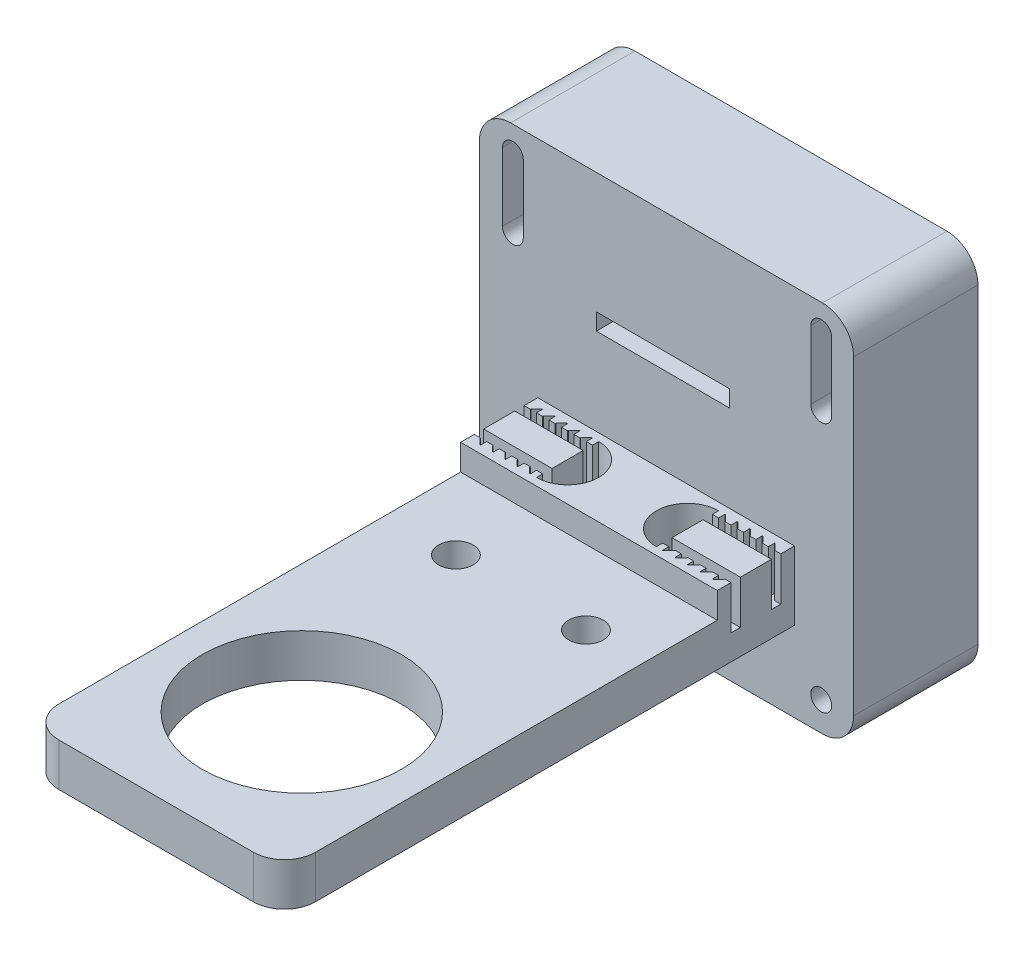
SolidWorks part; units mm, degrees
ref_plane "Alzado" through (0, 0, 0) normal (0, 0, 1) x (1, 0, 0)
ref_plane "Planta" through (0, 0, 0) normal (0, 1, 0) x (1, 0, 0)
ref_plane "Vista lateral" through (0, 0, 0) normal (1, 0, 0) x (0, 0, -1)
sketch "Croquis1" plane through (0, 0, 0) normal (0, 0, 1) x (1, 0, 0)
  line L0 (-21.7038, 24.1707) -> (-21.7038, 13.2033) construction
  line L1 (-27.0724, 28.25) -> (33.0729, 28.25)
  line L2 (-27.0724, 28.25) -> (-27.0724, -31.75)
  line L3 (-27.0724, -31.75) -> (33.0729, -31.75)
  line L4 (33.0729, 28.25) -> (33.0729, -31.75)
  line L5 (-8.2743, 8.8387) -> (13.1009, 8.8387)
  line L6 (-8.2743, 8.8387) -> (-8.2743, 6.1528)
  line L7 (-8.2743, 6.1528) -> (13.1009, 6.1528)
  line L8 (13.1009, 8.8387) -> (13.1009, 6.1528)
  line L9 (-20.0251, 24.1707) -> (-20.0251, 13.2033)
  line L10 (-23.3825, 24.1707) -> (-23.3825, 13.2033)
  line L11 (27.8733, 24.1707) -> (27.8733, 13.2033) construction
  line L12 (29.552, 24.1707) -> (29.552, 13.2033)
  line L13 (26.1946, 24.1707) -> (26.1946, 13.2033)
  circle A2 centre (27.8733, -27.0851) radius 1.6787
  circle A3 centre (-21.7038, -27.0851) radius 1.6787
  arc A4 (-20.0251, 24.1707) -> (-23.3825, 24.1707) centre (-21.7038, 24.1707) ccw
  arc A5 (-23.3825, 13.2033) -> (-20.0251, 13.2033) centre (-21.7038, 13.2033) ccw
  arc A6 (29.552, 24.1707) -> (26.1946, 24.1707) centre (27.8733, 24.1707) ccw
  arc A7 (26.1946, 13.2033) -> (29.552, 13.2033) centre (27.8733, 13.2033) ccw
  point P16 (-21.7038, 18.687)
  point P22 (27.8733, 18.687)
  dimension "D1" = 60.1453
  dimension "D2" = 60
extrude "Saliente-Extruir1" add sketch "Croquis1" along normal blind 20
sketch "Croquis2" plane through (0, 0, 20) normal (0, 0, 1) x (1, 0, 0)
  line L1 (-17.6867, -7.8196) -> (23.5792, -7.8196)
  line L2 (-17.6867, -7.8196) -> (-17.6867, -18.8667)
  line L3 (-17.6867, -18.8667) -> (23.5792, -18.8667)
  line L4 (23.5792, -7.8196) -> (23.5792, -18.8667)
extrude "Saliente-Extruir2" add sketch "Croquis2" along normal blind 82
sketch "Croquis3" plane through (23.5792, 0, 0) normal (1, 0, 0) x (0, 0, -1)
  line L1 (-54.9335, -4.4205) -> (-32.4143, -4.4205)
  line L2 (-54.9335, -4.4205) -> (-54.9335, -11.9623)
  line L3 (-54.9335, -11.9623) -> (-32.4143, -11.9623)
  line L4 (-32.4143, -11.9623) -> (-32.4143, -4.4205)
extrude "Cortar-Extruir1" cut sketch "Croquis3" against normal blind 50
sketch "Croquis4" plane through (0, -18.8667, 0) normal (0, -1, 0) x (1, 0, 0)
  circle A0 centre (-6.5237, 44.3331) radius 2.7788
  circle A1 centre (14.3869, 44.3331) radius 2.7788
extrude "Cortar-Extruir2" cut sketch "Croquis4" against normal blind 52
fillet "Redondeo1" radius 5 2 edges at (-17.6867, -13.3431, 102) (23.5792, -13.3431, 102)
fillet "Redondeo2" radius 5 4 edges at (-27.0724, 28.25, 10) (33.0729, 28.25, 10) (-27.0724, -31.75, 10) (33.0729, -31.75, 10)
sketch "Croquis5" plane through (0, -7.8196, 0) normal (0, 1, 0) x (1, 0, 0)
  circle A2 centre (2.9463, -78.5735) radius 16
extrude "Cortar-Extruir3" cut sketch "Croquis5" against normal blind 20
sketch "Croquis7" plane through (-17.6867, 0, 0) normal (-1, 0, 0) x (0, 0, 1)
  line L1 (54.9335, -7.8196) -> (107.4711, -7.8196)
  line L2 (54.9335, -7.8196) -> (54.9335, -11.9623)
  line L3 (54.9335, -11.9623) -> (107.4711, -11.9623)
  line L4 (107.4711, -7.8196) -> (107.4711, -11.9623)
extrude "Cortar-Extruir4" cut sketch "Croquis7" against normal blind 62
sketch "Croquis8" plane through (0, -7.8196, 0) normal (0, 1, 0) x (1, 0, 0)
  line L0 (-17.6867, -26.2072) -> (-6.6867, -26.2072) construction
  line L1 (-8.6867, -30.3072) -> (-7.7867, -31.2072)
  line L3 (-17.6867, -22.2072) -> (-6.6867, -22.2072) construction
  line L5 (-17.6867, -32.4143) -> (-17.6867, -20) construction
  line L6 (-13.6867, -22.2072) -> (-12.6867, -22.2072)
  line L7 (-17.6867, -22.2072) -> (-16.6867, -22.2072)
  line L8 (-11.6867, -22.2072) -> (-10.6867, -22.2072)
  line L9 (-17.6867, -23.7072) -> (-6.6867, -23.7072)
  line L10 (-17.6867, -22.2072) -> (-16.6867, -22.2072)
  line L11 (-9.6867, -22.2072) -> (-8.6867, -22.2072)
  line L12 (-7.6867, -22.2072) -> (-6.6867, -22.2072)
  line L13 (-16.6867, -22.2072) -> (-16.6867, -22.1072)
  line L14 (-15.7867, -21.2072) -> (-15.6867, -21.2072)
  line L15 (-15.6867, -21.2072) -> (-15.6867, -22.2072)
  line L16 (-16.6867, -22.1072) -> (-15.7867, -21.2072)
  line L17 (-15.6867, -22.2072) -> (-14.6867, -22.2072)
  line L18 (-15.6867, -22.2072) -> (-14.6867, -22.2072)
  line L19 (-15.6867, -22.2072) -> (-14.6867, -22.2072)
  line L20 (-14.6867, -22.2072) -> (-14.6867, -22.1072)
  line L21 (-13.7867, -21.2072) -> (-13.6867, -21.2072)
  line L22 (-13.6867, -21.2072) -> (-13.6867, -22.2072)
  line L23 (-14.6867, -22.1072) -> (-13.7867, -21.2072)
  line L24 (-13.6867, -22.2072) -> (-12.6867, -22.2072)
  line L25 (-13.6867, -22.2072) -> (-12.6867, -22.2072)
  line L26 (-12.6867, -22.2072) -> (-12.6867, -22.1072)
  line L27 (-11.7867, -21.2072) -> (-11.6867, -21.2072)
  line L28 (-11.6867, -21.2072) -> (-11.6867, -22.2072)
  line L29 (-12.6867, -22.1072) -> (-11.7867, -21.2072)
  line L30 (-11.6867, -22.2072) -> (-10.6867, -22.2072)
  line L31 (-11.6867, -22.2072) -> (-10.6867, -22.2072)
  line L32 (-10.6867, -22.2072) -> (-10.6867, -22.1072)
  line L33 (-9.7867, -21.2072) -> (-9.6867, -21.2072)
  line L34 (-9.6867, -21.2072) -> (-9.6867, -22.2072)
  line L35 (-10.6867, -22.1072) -> (-9.7867, -21.2072)
  line L36 (-9.6867, -22.2072) -> (-8.6867, -22.2072)
  line L37 (-9.6867, -22.2072) -> (-8.6867, -22.2072)
  line L38 (-8.6867, -22.2072) -> (-8.6867, -22.1072)
  line L39 (-7.7867, -21.2072) -> (-7.6867, -21.2072)
  line L40 (-7.6867, -21.2072) -> (-7.6867, -22.2072)
  line L41 (-8.6867, -22.1072) -> (-7.7867, -21.2072)
  line L42 (-17.6867, -28.7072) -> (-6.6867, -28.7072) construction
  line L43 (-17.6867, -30.2072) -> (-6.6867, -30.2072) construction
  line L44 (-7.6867, -31.2072) -> (-7.6867, -30.2072)
  line L45 (-7.7867, -31.2072) -> (-7.6867, -31.2072)
  line L46 (-8.6867, -30.2072) -> (-8.6867, -30.3072)
  line L47 (-9.6867, -30.2072) -> (-8.6867, -30.2072)
  line L48 (-9.6867, -30.2072) -> (-8.6867, -30.2072)
  line L49 (-10.6867, -30.3072) -> (-9.7867, -31.2072)
  line L50 (-9.6867, -31.2072) -> (-9.6867, -30.2072)
  line L51 (-9.7867, -31.2072) -> (-9.6867, -31.2072)
  line L52 (-10.6867, -30.2072) -> (-10.6867, -30.3072)
  line L53 (-11.6867, -30.2072) -> (-10.6867, -30.2072)
  line L54 (-11.6867, -30.2072) -> (-10.6867, -30.2072)
  line L55 (-12.6867, -30.3072) -> (-11.7867, -31.2072)
  line L56 (-11.6867, -31.2072) -> (-11.6867, -30.2072)
  line L57 (-11.7867, -31.2072) -> (-11.6867, -31.2072)
  line L58 (-12.6867, -30.2072) -> (-12.6867, -30.3072)
  line L59 (-13.6867, -30.2072) -> (-12.6867, -30.2072)
  line L60 (-13.6867, -30.2072) -> (-12.6867, -30.2072)
  line L61 (-14.6867, -30.3072) -> (-13.7867, -31.2072)
  line L62 (-13.6867, -31.2072) -> (-13.6867, -30.2072)
  line L63 (-13.7867, -31.2072) -> (-13.6867, -31.2072)
  line L64 (-14.6867, -30.2072) -> (-14.6867, -30.3072)
  line L65 (-15.6867, -30.2072) -> (-14.6867, -30.2072)
  line L66 (-15.6867, -30.2072) -> (-14.6867, -30.2072)
  line L67 (-15.6867, -30.2072) -> (-14.6867, -30.2072)
  line L68 (-16.6867, -30.3072) -> (-15.7867, -31.2072)
  line L69 (-15.6867, -31.2072) -> (-15.6867, -30.2072)
  line L70 (-15.7867, -31.2072) -> (-15.6867, -31.2072)
  line L71 (-16.6867, -30.2072) -> (-16.6867, -30.3072)
  line L72 (-7.6867, -30.2072) -> (-6.6867, -30.2072)
  line L73 (-9.6867, -30.2072) -> (-8.6867, -30.2072)
  line L74 (-17.6867, -30.2072) -> (-16.6867, -30.2072)
  line L75 (-17.6867, -28.7072) -> (-6.6867, -28.7072)
  line L76 (-11.6867, -30.2072) -> (-10.6867, -30.2072)
  line L77 (-17.6867, -30.2072) -> (-16.6867, -30.2072)
  line L78 (-13.6867, -30.2072) -> (-12.6867, -30.2072)
  line L79 (-6.6867, -21.2072) -> (-6.6867, -22.2072)
  line L80 (-6.6867, -30.2072) -> (-6.6867, -31.2072)
  line L81 (2.9463, -20) -> (2.9463, -32.4143)
  line L82 (23.5792, -20) -> (-17.6867, -20) construction
  line L83 (-17.6867, -32.4143) -> (23.5792, -32.4143) construction
  line L84 (12.5792, -30.2072) -> (12.5792, -31.2072)
  line L85 (12.5792, -21.2072) -> (12.5792, -22.2072)
  line L86 (19.5792, -30.2072) -> (18.5792, -30.2072)
  line L87 (23.5792, -30.2072) -> (22.5792, -30.2072)
  line L88 (17.5792, -30.2072) -> (16.5792, -30.2072)
  line L89 (23.5792, -28.7072) -> (12.5792, -28.7072)
  line L90 (23.5792, -30.2072) -> (22.5792, -30.2072)
  line L91 (15.5792, -30.2072) -> (14.5792, -30.2072)
  line L92 (13.5792, -30.2072) -> (12.5792, -30.2072)
  line L93 (22.5792, -30.2072) -> (22.5792, -30.3072)
  line L94 (21.6792, -31.2072) -> (21.5792, -31.2072)
  line L95 (21.5792, -31.2072) -> (21.5792, -30.2072)
  line L96 (22.5792, -30.3072) -> (21.6792, -31.2072)
  line L97 (21.5792, -30.2072) -> (20.5792, -30.2072)
  line L98 (21.5792, -30.2072) -> (20.5792, -30.2072)
  line L99 (21.5792, -30.2072) -> (20.5792, -30.2072)
  line L100 (20.5792, -30.2072) -> (20.5792, -30.3072)
  line L101 (19.6792, -31.2072) -> (19.5792, -31.2072)
  line L102 (19.5792, -31.2072) -> (19.5792, -30.2072)
  line L103 (20.5792, -30.3072) -> (19.6792, -31.2072)
  line L104 (19.5792, -30.2072) -> (18.5792, -30.2072)
  line L105 (19.5792, -30.2072) -> (18.5792, -30.2072)
  line L106 (18.5792, -30.2072) -> (18.5792, -30.3072)
  line L107 (17.6792, -31.2072) -> (17.5792, -31.2072)
  line L108 (17.5792, -31.2072) -> (17.5792, -30.2072)
  line L109 (18.5792, -30.3072) -> (17.6792, -31.2072)
  line L110 (17.5792, -30.2072) -> (16.5792, -30.2072)
  line L111 (17.5792, -30.2072) -> (16.5792, -30.2072)
  line L112 (16.5792, -30.2072) -> (16.5792, -30.3072)
  line L113 (15.6792, -31.2072) -> (15.5792, -31.2072)
  line L114 (15.5792, -31.2072) -> (15.5792, -30.2072)
  line L115 (16.5792, -30.3072) -> (15.6792, -31.2072)
  line L116 (15.5792, -30.2072) -> (14.5792, -30.2072)
  line L117 (15.5792, -30.2072) -> (14.5792, -30.2072)
  line L118 (14.5792, -30.2072) -> (14.5792, -30.3072)
  line L119 (13.6792, -31.2072) -> (13.5792, -31.2072)
  line L120 (13.5792, -31.2072) -> (13.5792, -30.2072)
  line L121 (14.5792, -22.1072) -> (13.6792, -21.2072)
  line L122 (13.5792, -21.2072) -> (13.5792, -22.2072)
  line L123 (13.6792, -21.2072) -> (13.5792, -21.2072)
  line L124 (14.5792, -22.2072) -> (14.5792, -22.1072)
  line L125 (15.5792, -22.2072) -> (14.5792, -22.2072)
  line L126 (15.5792, -22.2072) -> (14.5792, -22.2072)
  line L127 (16.5792, -22.1072) -> (15.6792, -21.2072)
  line L128 (15.5792, -21.2072) -> (15.5792, -22.2072)
  line L129 (15.6792, -21.2072) -> (15.5792, -21.2072)
  line L130 (16.5792, -22.2072) -> (16.5792, -22.1072)
  line L131 (17.5792, -22.2072) -> (16.5792, -22.2072)
  line L132 (17.5792, -22.2072) -> (16.5792, -22.2072)
  line L133 (18.5792, -22.1072) -> (17.6792, -21.2072)
  line L134 (17.5792, -21.2072) -> (17.5792, -22.2072)
  line L135 (17.6792, -21.2072) -> (17.5792, -21.2072)
  line L136 (18.5792, -22.2072) -> (18.5792, -22.1072)
  line L137 (19.5792, -22.2072) -> (18.5792, -22.2072)
  line L138 (19.5792, -22.2072) -> (18.5792, -22.2072)
  line L139 (20.5792, -22.1072) -> (19.6792, -21.2072)
  line L140 (19.5792, -21.2072) -> (19.5792, -22.2072)
  line L141 (19.6792, -21.2072) -> (19.5792, -21.2072)
  line L142 (20.5792, -22.2072) -> (20.5792, -22.1072)
  line L143 (21.5792, -22.2072) -> (20.5792, -22.2072)
  line L144 (21.5792, -22.2072) -> (20.5792, -22.2072)
  line L145 (21.5792, -22.2072) -> (20.5792, -22.2072)
  line L146 (22.5792, -22.1072) -> (21.6792, -21.2072)
  line L147 (21.5792, -21.2072) -> (21.5792, -22.2072)
  line L148 (21.6792, -21.2072) -> (21.5792, -21.2072)
  line L149 (22.5792, -22.2072) -> (22.5792, -22.1072)
  line L150 (13.5792, -22.2072) -> (12.5792, -22.2072)
  line L151 (15.5792, -22.2072) -> (14.5792, -22.2072)
  line L152 (23.5792, -22.2072) -> (22.5792, -22.2072)
  line L153 (23.5792, -23.7072) -> (12.5792, -23.7072)
  line L154 (17.5792, -22.2072) -> (16.5792, -22.2072)
  line L155 (23.5792, -22.2072) -> (22.5792, -22.2072)
  line L156 (19.5792, -22.2072) -> (18.5792, -22.2072)
  line L157 (14.5792, -30.3072) -> (13.6792, -31.2072)
  line L158 (-6.6867, -23.7072) -> (-6.6867, -28.7072)
  line L159 (-6.6867, -28.7072) -> (-6.8274, -28.7462)
  line L160 (-4.1867, -26.2072) -> (2.9508, -26.2072) construction
  line L161 (12.5792, -23.7072) -> (12.5792, -28.7072)
  arc A1 (-6.6867, -21.2072) -> (-6.6867, -31.2072) centre (-6.6867, -26.2072) cw
  arc A2 (12.5792, -21.2072) -> (12.5792, -31.2072) centre (12.5792, -26.2072) ccw
  arc A3 (-6.6867, -22.2072) -> (-6.6867, -30.2072) centre (-6.6867, -26.2072) cw construction
  arc A4 (-6.6867, -23.7072) -> (-6.6867, -28.7072) centre (-6.6867, -26.2072) cw construction
  point P28 (-16.6867, -21.2072)
  point P37 (-14.6867, -21.2072)
  point P44 (-12.6867, -21.2072)
  point P51 (-10.6867, -21.2072)
  point P58 (-8.6867, -21.2072)
  point P78 (-8.6867, -31.2072)
  point P79 (-10.6867, -31.2072)
  point P80 (-12.6867, -31.2072)
  point P81 (-14.6867, -31.2072)
  point P82 (-16.6867, -31.2072)
  point P96 (22.5792, -31.2072)
  point P155 (20.5792, -31.2072)
  point P156 (18.5792, -31.2072)
  point P157 (16.5792, -31.2072)
  point P158 (14.5792, -31.2072)
  point P159 (14.5792, -21.2072)
  point P160 (16.5792, -21.2072)
  point P161 (18.5792, -21.2072)
  point P162 (20.5792, -21.2072)
  point P163 (22.5792, -21.2072)
  line M2 (-17.6867, -20) -> (-17.6867, -32.4143)
  line M4 (23.5792, -32.4143) -> (23.5792, -20)
  dimension "D2" = 1
  dimension "D3" = 1.5
  dimension "D4" = 1
  dimension "D5" = 1
  dimension "D6" = 5
extrude "Cortar-Extruir5" cut sketch "Croquis8" against normal blind 7 contours A1 L79 L12 L40 L39 L41 L38 L11 L34 L33 L35 L32 L8 L28 L27 L29 L26 L6 L22 L21 L23 L20 L17 L15 L14 L16 L13 L7 L9 L75 L74 L71 L68 L70 L69 L65 L64 L61 L63 L62 L59 L58 L55 L57 L56 L53 L52 L49 M2 | L161 L153 L152 L149 L146 L148 L147 L143 L142 L139 L141 L140 L137 L136 L133 L135 L134 L131 L130 L127 L129 L128 L125 L124 L121 L123 L122 L150 L85 A2 L84 L92 L120 L119 L157 L118 L91 L114 L113 L115 L112 L88 L108 L107 L109 L106 L86 L102 L101 L103 M4 region at (-8.498, -7.8196, 30.2572) region at (12.3905, -7.8196, 30.7072)
